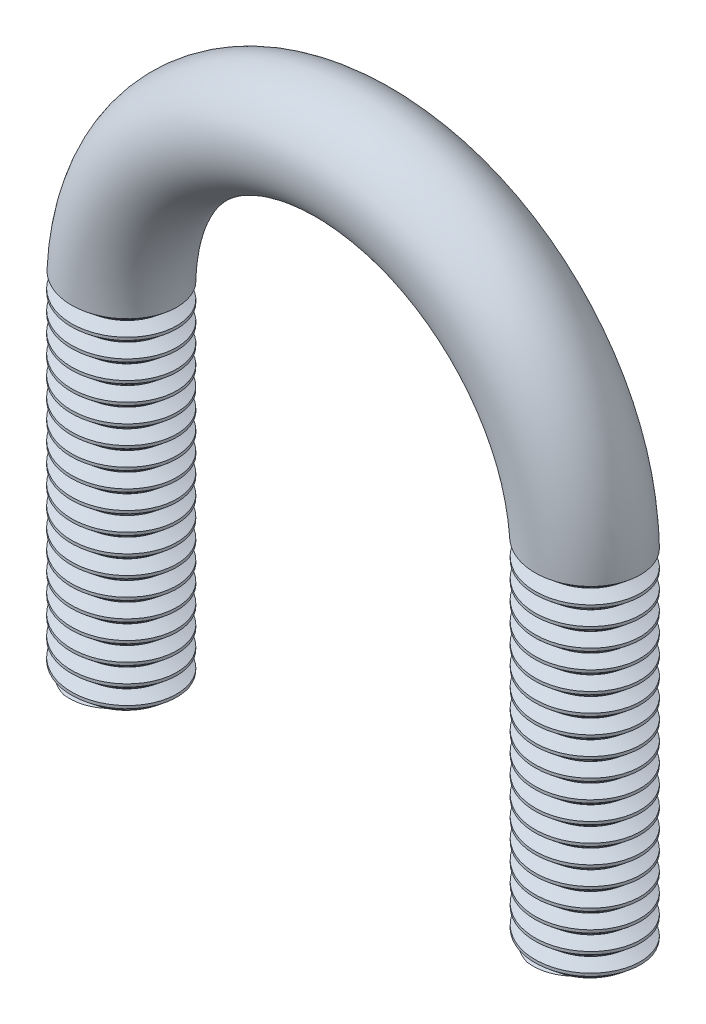
SolidWorks part; units mm, degrees
material "AISI 1020"
ref_plane "Front" through (0, 0, 0) normal (0, 0, 1) x (1, 0, 0)
ref_plane "Top" through (0, 0, 0) normal (0, 1, 0) x (1, 0, 0)
ref_plane "Right" through (0, 0, 0) normal (1, 0, 0) x (0, 0, -1)
sketch "Sketch1" plane through (0, 0, 0) normal (0, 0, 1) x (1, 0, 0)
  line L0 (17.4308, -8.251) -> (17.4308, 17.235)
  line L2 (-17.4308, -8.251) -> (-17.4308, 17.235)
  line L4 (0, -14.6685) -> (0, 64.7717) construction
  arc A0 (17.4308, 17.235) -> (-17.4308, 17.235) centre (0, 17.235) ccw
  dimension "0.61*TubeDia" = 17.4308
  dimension "0.28875*TubeDia" = 8.251
  dimension "0.8919*TubeDia" = 25.486
ref_plane "Plane1" through (0, -8.251, 0) normal (0, 1, 0) x (1, 0, 0)
sketch "Sketch2" plane through (0, -8.251, 0) normal (0, 1, 0) x (1, 0, 0)
  line L0 (-17.4308, 0) -> (17.4308, 0) construction
  circle A0 centre (-17.4308, 0) radius 3.9687
  dimension "D1" = 7.9375
sweep "Sweep1" add profiles "Sketch2" path "Sketch1"
chamfer "Chamfer1" distance 0.508 angle 45 2 edges at (17.4308, -8.251, 3.9687) (-17.4308, -8.251, 3.9687)
ref_plane "Plane2" through (0, -10.791, 0) normal (0, 1, 0) x (1, 0, 0)
sketch "Sketch3" plane through (0, -10.791, 0) normal (0, 1, 0) x (1, 0, 0)
  circle A0 centre (-17.4308, 0) radius 3.9688
  circle A1 centre (-17.4308, 0) radius 3.9687 construction
curve "Helix/Spiral1" pitch 1.4111 height 28.575 radius 3.9688 left hand yes centre (-17.4308, -10.791, 0) axis (0, 1, 0) start towards (0, 0, 1) parameters "0.5625*TubeDia"=28.575, "ThreadLead"=1.4111
sketch "Sketch4" plane through (0, 0, 0) normal (0, 0, 1) x (1, 0, 0)
  line L0 (-21.3995, 17.235) -> (-21.3995, -7.743) construction
  line L1 (-20.3967, 17.6207) -> (-21.7595, 18.734)
  line L2 (-21.7595, 18.734) -> (-22.0423, 16.9971)
  line L3 (-22.0423, 16.9971) -> (-20.3967, 17.6207)
  circle A0 centre (-21.3995, 17.784) radius 0.508 construction
  spline S0 degree 3 poles (-17.4308, -10.791) (-17.9469, -10.7618) (-18.9906, -10.7027) (-20.3097, -10.6147) (-21.193, -10.5264) (-21.5028, -10.4383) (-21.1929, -10.3501) (-20.3101, -10.2619) (-18.9891, -10.1737) (-17.4307, -10.0855) (-15.8724, -9.9973) (-14.5514, -9.9091) (-13.6686, -9.8209) (-13.3587, -9.7327) (-13.6686, -9.6445) (-14.5514, -9.5563) (-15.8724, -9.4681) (-17.4307, -9.3799) (-18.9891, -9.2917) (-20.3101, -9.2035) (-21.1929, -9.1153) (-21.5028, -9.0271) (-21.1929, -8.9389) (-20.3101, -8.8508) (-18.9891, -8.7626) (-17.4307, -8.6744) (-15.8724, -8.5862) (-14.5514, -8.498) (-13.6686, -8.4098) (-13.3587, -8.3216) (-13.6686, -8.2334) (-14.5514, -8.1452) (-15.8724, -8.057) (-17.4308, -7.9688) (-18.9891, -7.8806) (-20.3101, -7.7924) (-21.1929, -7.7042) (-21.5028, -7.616) (-21.1929, -7.5278) (-20.3101, -7.4396) (-18.9891, -7.3514) (-17.4307, -7.2633) (-15.8724, -7.1751) (-14.5514, -7.0869) (-13.6686, -6.9987) (-13.3587, -6.9105) (-13.6686, -6.8223) (-14.5514, -6.7341) (-15.8724, -6.6459) (-17.4308, -6.5577) (-18.9891, -6.4695) (-20.3101, -6.3813) (-21.1929, -6.2931) (-21.5028, -6.2049) (-21.1929, -6.1167) (-20.3101, -6.0285) (-18.9891, -5.9403) (-17.4307, -5.8521) (-15.8724, -5.7639) (-14.5514, -5.6758) (-13.6686, -5.5876) (-13.3587, -5.4994) (-13.6686, -5.4112) (-14.5514, -5.323) (-15.8724, -5.2348) (-17.4308, -5.1466) (-18.9891, -5.0584) (-20.3101, -4.9702) (-21.1929, -4.882) (-21.5028, -4.7938) (-21.1929, -4.7056) (-20.3101, -4.6174) (-18.9891, -4.5292) (-17.4307, -4.441) (-15.8724, -4.3528) (-14.5514, -4.2646) (-13.6686, -4.1764) (-13.3587, -4.0883) (-13.6686, -4.0001) (-14.5514, -3.9119) (-15.8724, -3.8237) (-17.4308, -3.7355) (-18.9891, -3.6473) (-20.3101, -3.5591) (-21.1929, -3.4709) (-21.5028, -3.3827) (-21.1929, -3.2945) (-20.3101, -3.2063) (-18.9891, -3.1181) (-17.4307, -3.0299) (-15.8724, -2.9417) (-14.5514, -2.8535) (-13.6686, -2.7653) (-13.3587, -2.6771) (-13.6686, -2.5889) (-14.5514, -2.5008) (-15.8724, -2.4126) (-17.4308, -2.3244) (-18.9891, -2.2362) (-20.3101, -2.148) (-21.1929, -2.0598) (-21.5028, -1.9716) (-21.1929, -1.8834) (-20.3101, -1.7952) (-18.9891, -1.707) (-17.4307, -1.6188) (-15.8724, -1.5306) (-14.5514, -1.4424) (-13.6686, -1.3542) (-13.3587, -1.266) (-13.6686, -1.1778) (-14.5514, -1.0896) (-15.8724, -1.0014) (-17.4308, -0.9133) (-18.9891, -0.8251) (-20.3101, -0.7369) (-21.1929, -0.6487) (-21.5028, -0.5605) (-21.1929, -0.4723) (-20.3101, -0.3841) (-18.9891, -0.2959) (-17.4307, -0.2077) (-15.8724, -0.1195) (-14.5514, -0.0313) (-13.6686, 0.0569) (-13.3587, 0.1451) (-13.6686, 0.2333) (-14.5514, 0.3215) (-15.8724, 0.4097) (-17.4308, 0.4979) (-18.9891, 0.5861) (-20.3101, 0.6742) (-21.1929, 0.7624) (-21.5028, 0.8506) (-21.1929, 0.9388) (-20.3101, 1.027) (-18.9891, 1.1152) (-17.4307, 1.2034) (-15.8724, 1.2916) (-14.5514, 1.3798) (-13.6686, 1.468) (-13.3587, 1.5562) (-13.6686, 1.6444) (-14.5514, 1.7326) (-15.8724, 1.8208) (-17.4308, 1.909) (-18.9891, 1.9972) (-20.3101, 2.0854) (-21.1929, 2.1736) (-21.5028, 2.2617) (-21.1929, 2.3499) (-20.3101, 2.4381) (-18.9891, 2.5263) (-17.4307, 2.6145) (-15.8724, 2.7027) (-14.5514, 2.7909) (-13.6686, 2.8791) (-13.3587, 2.9673) (-13.6686, 3.0555) (-14.5514, 3.1437) (-15.8724, 3.2319) (-17.4308, 3.3201) (-18.9891, 3.4083) (-20.3101, 3.4965) (-21.1929, 3.5847) (-21.5028, 3.6729) (-21.1929, 3.7611) (-20.3101, 3.8492) (-18.9891, 3.9374) (-17.4307, 4.0256) (-15.8724, 4.1138) (-14.5514, 4.202) (-13.6686, 4.2902) (-13.3587, 4.3784) (-13.6686, 4.4666) (-14.5514, 4.5548) (-15.8724, 4.643) (-17.4308, 4.7312) (-18.9891, 4.8194) (-20.3101, 4.9076) (-21.1929, 4.9958) (-21.5028, 5.084) (-21.1929, 5.1722) (-20.3101, 5.2604) (-18.9891, 5.3486) (-17.4307, 5.4367) (-15.8724, 5.5249) (-14.5514, 5.6131) (-13.6686, 5.7013) (-13.3587, 5.7895) (-13.6686, 5.8777) (-14.5514, 5.9659) (-15.8724, 6.0541) (-17.4308, 6.1423) (-18.9891, 6.2305) (-20.3101, 6.3187) (-21.1929, 6.4069) (-21.5028, 6.4951) (-21.1929, 6.5833) (-20.3101, 6.6715) (-18.9891, 6.7597) (-17.4307, 6.8479) (-15.8724, 6.9361) (-14.5514, 7.0242) (-13.6686, 7.1124) (-13.3587, 7.2006) (-13.6686, 7.2888) (-14.5514, 7.377) (-15.8724, 7.4652) (-17.4308, 7.5534) (-18.9891, 7.6416) (-20.3101, 7.7298) (-21.1929, 7.818) (-21.5028, 7.9062) (-21.1929, 7.9944) (-20.3101, 8.0826) (-18.9891, 8.1708) (-17.4307, 8.259) (-15.8724, 8.3472) (-14.5514, 8.4354) (-13.6686, 8.5236) (-13.3587, 8.6117) (-13.6686, 8.6999) (-14.5514, 8.7881) (-15.8724, 8.8763) (-17.4308, 8.9645) (-18.9891, 9.0527) (-20.3101, 9.1409) (-21.1929, 9.2291) (-21.5028, 9.3173) (-21.1929, 9.4055) (-20.3101, 9.4937) (-18.9891, 9.5819) (-17.4307, 9.6701) (-15.8724, 9.7583) (-14.5514, 9.8465) (-13.6686, 9.9347) (-13.3587, 10.0229) (-13.6686, 10.1111) (-14.5514, 10.1992) (-15.8724, 10.2874) (-17.4308, 10.3756) (-18.9891, 10.4638) (-20.3101, 10.552) (-21.1929, 10.6402) (-21.5028, 10.7284) (-21.1929, 10.8166) (-20.3101, 10.9048) (-18.9891, 10.993) (-17.4307, 11.0812) (-15.8724, 11.1694) (-14.5514, 11.2576) (-13.6686, 11.3458) (-13.3587, 11.434) (-13.6686, 11.5222) (-14.5514, 11.6104) (-15.8724, 11.6986) (-17.4308, 11.7867) (-18.9891, 11.8749) (-20.3101, 11.9631) (-21.1929, 12.0513) (-21.5028, 12.1395) (-21.1929, 12.2277) (-20.3101, 12.3159) (-18.9891, 12.4041) (-17.4307, 12.4923) (-15.8724, 12.5805) (-14.5514, 12.6687) (-13.6686, 12.7569) (-13.3587, 12.8451) (-13.6686, 12.9333) (-14.5514, 13.0215) (-15.8724, 13.1097) (-17.4308, 13.1979) (-18.9891, 13.2861) (-20.3101, 13.3742) (-21.1929, 13.4624) (-21.5028, 13.5506) (-21.1929, 13.6388) (-20.3101, 13.727) (-18.9891, 13.8152) (-17.4307, 13.9034) (-15.8724, 13.9916) (-14.5514, 14.0798) (-13.6686, 14.168) (-13.3587, 14.2562) (-13.6686, 14.3444) (-14.5514, 14.4326) (-15.8724, 14.5208) (-17.4308, 14.609) (-18.9891, 14.6972) (-20.3101, 14.7854) (-21.1929, 14.8736) (-21.5028, 14.9617) (-21.1929, 15.0499) (-20.3101, 15.1381) (-18.9891, 15.2263) (-17.4307, 15.3145) (-15.8724, 15.4027) (-14.5514, 15.4909) (-13.6686, 15.5791) (-13.3587, 15.6673) (-13.6686, 15.7555) (-14.5514, 15.8437) (-15.8724, 15.9319) (-17.4308, 16.0201) (-18.9891, 16.1083) (-20.3101, 16.1965) (-21.1929, 16.2847) (-21.5028, 16.3729) (-21.1929, 16.4611) (-20.3101, 16.5492) (-18.9891, 16.6374) (-17.4307, 16.7256) (-15.8724, 16.8138) (-14.5514, 16.902) (-13.6686, 16.9902) (-13.3587, 17.0784) (-13.6686, 17.1666) (-14.5514, 17.2548) (-15.8724, 17.343) (-17.4308, 17.4312) (-18.9891, 17.5194) (-20.3101, 17.6076) (-21.1929, 17.6957) (-21.3995, 17.7548) (-21.3995, 17.784) knots 0 0 0 0 0.003086 0.006173 0.009259 0.012346 0.015432 0.018519 0.021605 0.024691 0.027778 0.030864 0.033951 0.037037 0.040123 0.04321 0.046296 0.049383 0.052469 0.055556 0.058642 0.061728 0.064815 0.067901 0.070988 0.074074 0.07716 0.080247 0.083333 0.08642 0.089506 0.092593 0.095679 0.098765 0.101852 0.104938 0.108025 0.111111 0.114198 0.117284 0.12037 0.123457 0.126543 0.12963 0.132716 0.135802 0.138889 0.141975 0.145062 0.148148 0.151235 0.154321 0.157407 0.160494 0.16358 0.166667 0.169753 0.17284 0.175926 0.179012 0.182099 0.185185 0.188272 0.191358 0.194444 0.197531 0.200617 0.203704 0.20679 0.209877 0.212963 0.216049 0.219136 0.222222 0.225309 0.228395 0.231481 0.234568 0.237654 0.240741 0.243827 0.246914 0.25 0.253086 0.256173 0.259259 0.262346 0.265432 0.268519 0.271605 0.274691 0.277778 0.280864 0.283951 0.287037 0.290123 0.29321 0.296296 0.299383 0.302469 0.305556 0.308642 0.311728 0.314815 0.317901 0.320988 0.324074 0.32716 0.330247 0.333333 0.33642 0.339506 0.342593 0.345679 0.348765 0.351852 0.354938 0.358025 0.361111 0.364198 0.367284 0.37037 0.373457 0.376543 0.37963 0.382716 0.385802 0.388889 0.391975 0.395062 0.398148 0.401235 0.404321 0.407407 0.410494 0.41358 0.416667 0.419753 0.42284 0.425926 0.429012 0.432099 0.435185 0.438272 0.441358 0.444444 0.447531 0.450617 0.453704 0.45679 0.459877 0.462963 0.466049 0.469136 0.472222 0.475309 0.478395 0.481481 0.484568 0.487654 0.490741 0.493827 0.496914 0.5 0.503086 0.506173 0.509259 0.512346 0.515432 0.518519 0.521605 0.524691 0.527778 0.530864 0.533951 0.537037 0.540123 0.54321 0.546296 0.549383 0.552469 0.555556 0.558642 0.561728 0.564815 0.567901 0.570988 0.574074 0.57716 0.580247 0.583333 0.58642 0.589506 0.592593 0.595679 0.598765 0.601852 0.604938 0.608025 0.611111 0.614198 0.617284 0.62037 0.623457 0.626543 0.62963 0.632716 0.635802 0.638889 0.641975 0.645062 0.648148 0.651235 0.654321 0.657407 0.660494 0.66358 0.666667 0.669753 0.67284 0.675926 0.679012 0.682099 0.685185 0.688272 0.691358 0.694444 0.697531 0.700617 0.703704 0.70679 0.709877 0.712963 0.716049 0.719136 0.722222 0.725309 0.728395 0.731481 0.734568 0.737654 0.740741 0.743827 0.746914 0.75 0.753086 0.756173 0.759259 0.762346 0.765432 0.768519 0.771605 0.774691 0.777778 0.780864 0.783951 0.787037 0.790123 0.79321 0.796296 0.799383 0.802469 0.805556 0.808642 0.811728 0.814815 0.817901 0.820988 0.824074 0.82716 0.830247 0.833333 0.83642 0.839506 0.842593 0.845679 0.848765 0.851852 0.854938 0.858025 0.861111 0.864198 0.867284 0.87037 0.873457 0.876543 0.87963 0.882716 0.885802 0.888889 0.891975 0.895062 0.898148 0.901235 0.904321 0.907407 0.910494 0.91358 0.916667 0.919753 0.92284 0.925926 0.929012 0.932099 0.935185 0.938272 0.941358 0.944444 0.947531 0.950617 0.953704 0.95679 0.959877 0.962963 0.966049 0.969136 0.972222 0.975309 0.978395 0.981481 0.984568 0.987654 0.990741 0.993827 0.996914 1 1 1 1 construction
  dimension "ThdDepth" = 1.016
sweep "Cut-Sweep1" cut profiles "Sketch4" path "Helix/Spiral1"
sketch "Sketch5" plane through (0, -10.791, 0) normal (0, 1, 0) x (1, 0, 0)
  circle A0 centre (17.4308, 0) radius 3.9687
  circle A1 centre (17.4308, 0) radius 3.9687 construction
curve "Helix/Spiral2" pitch 1.4111 height 28.575 radius 3.9687 left hand yes centre (17.4308, -10.791, 0) axis (0, 1, 0) start towards (0, 0, 1) parameters "ThdLength"=28.575
sketch "Sketch6" plane through (0, 0, 0) normal (0, 0, 1) x (1, 0, 0)
  line L0 (13.462, 17.235) -> (13.462, -7.743) construction
  line L1 (14.4648, 17.6207) -> (13.102, 18.734)
  line L2 (13.102, 18.734) -> (12.8192, 16.9971)
  line L3 (12.8192, 16.9971) -> (14.4648, 17.6207)
  circle A0 centre (13.462, 17.784) radius 0.508 construction
  spline S0 degree 3 poles (17.4308, -10.791) (16.9146, -10.7618) (15.8709, -10.7027) (14.5518, -10.6147) (13.6685, -10.5264) (13.3587, -10.4383) (13.6686, -10.3501) (14.5514, -10.2619) (15.8724, -10.1737) (17.4308, -10.0855) (18.9891, -9.9973) (20.3101, -9.9091) (21.1929, -9.8209) (21.5028, -9.7327) (21.1929, -9.6445) (20.3101, -9.5563) (18.9891, -9.4681) (17.4308, -9.3799) (15.8724, -9.2917) (14.5514, -9.2035) (13.6686, -9.1153) (13.3587, -9.0271) (13.6686, -8.9389) (14.5514, -8.8508) (15.8724, -8.7626) (17.4308, -8.6744) (18.9891, -8.5862) (20.3101, -8.498) (21.1929, -8.4098) (21.5028, -8.3216) (21.1929, -8.2334) (20.3101, -8.1452) (18.9891, -8.057) (17.4307, -7.9688) (15.8724, -7.8806) (14.5514, -7.7924) (13.6686, -7.7042) (13.3587, -7.616) (13.6686, -7.5278) (14.5514, -7.4396) (15.8724, -7.3514) (17.4308, -7.2633) (18.9891, -7.1751) (20.3101, -7.0869) (21.1929, -6.9987) (21.5028, -6.9105) (21.1929, -6.8223) (20.3101, -6.7341) (18.9891, -6.6459) (17.4307, -6.5577) (15.8724, -6.4695) (14.5514, -6.3813) (13.6686, -6.2931) (13.3587, -6.2049) (13.6686, -6.1167) (14.5514, -6.0285) (15.8724, -5.9403) (17.4308, -5.8521) (18.9891, -5.7639) (20.3101, -5.6758) (21.1929, -5.5876) (21.5028, -5.4994) (21.1929, -5.4112) (20.3101, -5.323) (18.9891, -5.2348) (17.4307, -5.1466) (15.8724, -5.0584) (14.5514, -4.9702) (13.6686, -4.882) (13.3587, -4.7938) (13.6686, -4.7056) (14.5514, -4.6174) (15.8724, -4.5292) (17.4308, -4.441) (18.9891, -4.3528) (20.3101, -4.2646) (21.1929, -4.1764) (21.5028, -4.0883) (21.1929, -4.0001) (20.3101, -3.9119) (18.9891, -3.8237) (17.4307, -3.7355) (15.8724, -3.6473) (14.5514, -3.5591) (13.6686, -3.4709) (13.3587, -3.3827) (13.6686, -3.2945) (14.5514, -3.2063) (15.8724, -3.1181) (17.4308, -3.0299) (18.9891, -2.9417) (20.3101, -2.8535) (21.1929, -2.7653) (21.5028, -2.6771) (21.1929, -2.5889) (20.3101, -2.5008) (18.9891, -2.4126) (17.4307, -2.3244) (15.8724, -2.2362) (14.5514, -2.148) (13.6686, -2.0598) (13.3587, -1.9716) (13.6686, -1.8834) (14.5514, -1.7952) (15.8724, -1.707) (17.4308, -1.6188) (18.9891, -1.5306) (20.3101, -1.4424) (21.1929, -1.3542) (21.5028, -1.266) (21.1929, -1.1778) (20.3101, -1.0896) (18.9891, -1.0014) (17.4307, -0.9133) (15.8724, -0.8251) (14.5514, -0.7369) (13.6686, -0.6487) (13.3587, -0.5605) (13.6686, -0.4723) (14.5514, -0.3841) (15.8724, -0.2959) (17.4308, -0.2077) (18.9891, -0.1195) (20.3101, -0.0313) (21.1929, 0.0569) (21.5028, 0.1451) (21.1929, 0.2333) (20.3101, 0.3215) (18.9891, 0.4097) (17.4307, 0.4979) (15.8724, 0.5861) (14.5514, 0.6742) (13.6686, 0.7624) (13.3587, 0.8506) (13.6686, 0.9388) (14.5514, 1.027) (15.8724, 1.1152) (17.4308, 1.2034) (18.9891, 1.2916) (20.3101, 1.3798) (21.1929, 1.468) (21.5028, 1.5562) (21.1929, 1.6444) (20.3101, 1.7326) (18.9891, 1.8208) (17.4307, 1.909) (15.8724, 1.9972) (14.5514, 2.0854) (13.6686, 2.1736) (13.3587, 2.2617) (13.6686, 2.3499) (14.5514, 2.4381) (15.8724, 2.5263) (17.4308, 2.6145) (18.9891, 2.7027) (20.3101, 2.7909) (21.1929, 2.8791) (21.5028, 2.9673) (21.1929, 3.0555) (20.3101, 3.1437) (18.9891, 3.2319) (17.4307, 3.3201) (15.8724, 3.4083) (14.5514, 3.4965) (13.6686, 3.5847) (13.3587, 3.6729) (13.6686, 3.7611) (14.5514, 3.8492) (15.8724, 3.9374) (17.4308, 4.0256) (18.9891, 4.1138) (20.3101, 4.202) (21.1929, 4.2902) (21.5028, 4.3784) (21.1929, 4.4666) (20.3101, 4.5548) (18.9891, 4.643) (17.4307, 4.7312) (15.8724, 4.8194) (14.5514, 4.9076) (13.6686, 4.9958) (13.3587, 5.084) (13.6686, 5.1722) (14.5514, 5.2604) (15.8724, 5.3486) (17.4308, 5.4367) (18.9891, 5.5249) (20.3101, 5.6131) (21.1929, 5.7013) (21.5028, 5.7895) (21.1929, 5.8777) (20.3101, 5.9659) (18.9891, 6.0541) (17.4307, 6.1423) (15.8724, 6.2305) (14.5514, 6.3187) (13.6686, 6.4069) (13.3587, 6.4951) (13.6686, 6.5833) (14.5514, 6.6715) (15.8724, 6.7597) (17.4308, 6.8479) (18.9891, 6.9361) (20.3101, 7.0242) (21.1929, 7.1124) (21.5028, 7.2006) (21.1929, 7.2888) (20.3101, 7.377) (18.9891, 7.4652) (17.4307, 7.5534) (15.8724, 7.6416) (14.5514, 7.7298) (13.6686, 7.818) (13.3587, 7.9062) (13.6686, 7.9944) (14.5514, 8.0826) (15.8724, 8.1708) (17.4308, 8.259) (18.9891, 8.3472) (20.3101, 8.4354) (21.1929, 8.5236) (21.5028, 8.6117) (21.1929, 8.6999) (20.3101, 8.7881) (18.9891, 8.8763) (17.4307, 8.9645) (15.8724, 9.0527) (14.5514, 9.1409) (13.6686, 9.2291) (13.3587, 9.3173) (13.6686, 9.4055) (14.5514, 9.4937) (15.8724, 9.5819) (17.4308, 9.6701) (18.9891, 9.7583) (20.3101, 9.8465) (21.1929, 9.9347) (21.5028, 10.0229) (21.1929, 10.1111) (20.3101, 10.1992) (18.9891, 10.2874) (17.4307, 10.3756) (15.8724, 10.4638) (14.5514, 10.552) (13.6686, 10.6402) (13.3587, 10.7284) (13.6686, 10.8166) (14.5514, 10.9048) (15.8724, 10.993) (17.4308, 11.0812) (18.9891, 11.1694) (20.3101, 11.2576) (21.1929, 11.3458) (21.5028, 11.434) (21.1929, 11.5222) (20.3101, 11.6104) (18.9891, 11.6986) (17.4307, 11.7867) (15.8724, 11.8749) (14.5514, 11.9631) (13.6686, 12.0513) (13.3587, 12.1395) (13.6686, 12.2277) (14.5514, 12.3159) (15.8724, 12.4041) (17.4308, 12.4923) (18.9891, 12.5805) (20.3101, 12.6687) (21.1929, 12.7569) (21.5028, 12.8451) (21.1929, 12.9333) (20.3101, 13.0215) (18.9891, 13.1097) (17.4307, 13.1979) (15.8724, 13.2861) (14.5514, 13.3742) (13.6686, 13.4624) (13.3587, 13.5506) (13.6686, 13.6388) (14.5514, 13.727) (15.8724, 13.8152) (17.4308, 13.9034) (18.9891, 13.9916) (20.3101, 14.0798) (21.1929, 14.168) (21.5028, 14.2562) (21.1929, 14.3444) (20.3101, 14.4326) (18.9891, 14.5208) (17.4307, 14.609) (15.8724, 14.6972) (14.5514, 14.7854) (13.6686, 14.8736) (13.3587, 14.9617) (13.6686, 15.0499) (14.5514, 15.1381) (15.8724, 15.2263) (17.4308, 15.3145) (18.9891, 15.4027) (20.3101, 15.4909) (21.1929, 15.5791) (21.5028, 15.6673) (21.1929, 15.7555) (20.3101, 15.8437) (18.9891, 15.9319) (17.4307, 16.0201) (15.8724, 16.1083) (14.5514, 16.1965) (13.6686, 16.2847) (13.3587, 16.3729) (13.6686, 16.4611) (14.5514, 16.5492) (15.8724, 16.6374) (17.4308, 16.7256) (18.9891, 16.8138) (20.3101, 16.902) (21.1929, 16.9902) (21.5028, 17.0784) (21.1929, 17.1666) (20.3101, 17.2548) (18.9891, 17.343) (17.4307, 17.4312) (15.8724, 17.5194) (14.5514, 17.6076) (13.6686, 17.6957) (13.462, 17.7548) (13.462, 17.784) knots 0 0 0 0 0.003086 0.006173 0.009259 0.012346 0.015432 0.018519 0.021605 0.024691 0.027778 0.030864 0.033951 0.037037 0.040123 0.04321 0.046296 0.049383 0.052469 0.055556 0.058642 0.061728 0.064815 0.067901 0.070988 0.074074 0.07716 0.080247 0.083333 0.08642 0.089506 0.092593 0.095679 0.098765 0.101852 0.104938 0.108025 0.111111 0.114198 0.117284 0.12037 0.123457 0.126543 0.12963 0.132716 0.135802 0.138889 0.141975 0.145062 0.148148 0.151235 0.154321 0.157407 0.160494 0.16358 0.166667 0.169753 0.17284 0.175926 0.179012 0.182099 0.185185 0.188272 0.191358 0.194444 0.197531 0.200617 0.203704 0.20679 0.209877 0.212963 0.216049 0.219136 0.222222 0.225309 0.228395 0.231481 0.234568 0.237654 0.240741 0.243827 0.246914 0.25 0.253086 0.256173 0.259259 0.262346 0.265432 0.268519 0.271605 0.274691 0.277778 0.280864 0.283951 0.287037 0.290123 0.29321 0.296296 0.299383 0.302469 0.305556 0.308642 0.311728 0.314815 0.317901 0.320988 0.324074 0.32716 0.330247 0.333333 0.33642 0.339506 0.342593 0.345679 0.348765 0.351852 0.354938 0.358025 0.361111 0.364198 0.367284 0.37037 0.373457 0.376543 0.37963 0.382716 0.385802 0.388889 0.391975 0.395062 0.398148 0.401235 0.404321 0.407407 0.410494 0.41358 0.416667 0.419753 0.42284 0.425926 0.429012 0.432099 0.435185 0.438272 0.441358 0.444444 0.447531 0.450617 0.453704 0.45679 0.459877 0.462963 0.466049 0.469136 0.472222 0.475309 0.478395 0.481481 0.484568 0.487654 0.490741 0.493827 0.496914 0.5 0.503086 0.506173 0.509259 0.512346 0.515432 0.518519 0.521605 0.524691 0.527778 0.530864 0.533951 0.537037 0.540123 0.54321 0.546296 0.549383 0.552469 0.555556 0.558642 0.561728 0.564815 0.567901 0.570988 0.574074 0.57716 0.580247 0.583333 0.58642 0.589506 0.592593 0.595679 0.598765 0.601852 0.604938 0.608025 0.611111 0.614198 0.617284 0.62037 0.623457 0.626543 0.62963 0.632716 0.635802 0.638889 0.641975 0.645062 0.648148 0.651235 0.654321 0.657407 0.660494 0.66358 0.666667 0.669753 0.67284 0.675926 0.679012 0.682099 0.685185 0.688272 0.691358 0.694444 0.697531 0.700617 0.703704 0.70679 0.709877 0.712963 0.716049 0.719136 0.722222 0.725309 0.728395 0.731481 0.734568 0.737654 0.740741 0.743827 0.746914 0.75 0.753086 0.756173 0.759259 0.762346 0.765432 0.768519 0.771605 0.774691 0.777778 0.780864 0.783951 0.787037 0.790123 0.79321 0.796296 0.799383 0.802469 0.805556 0.808642 0.811728 0.814815 0.817901 0.820988 0.824074 0.82716 0.830247 0.833333 0.83642 0.839506 0.842593 0.845679 0.848765 0.851852 0.854938 0.858025 0.861111 0.864198 0.867284 0.87037 0.873457 0.876543 0.87963 0.882716 0.885802 0.888889 0.891975 0.895062 0.898148 0.901235 0.904321 0.907407 0.910494 0.91358 0.916667 0.919753 0.92284 0.925926 0.929012 0.932099 0.935185 0.938272 0.941358 0.944444 0.947531 0.950617 0.953704 0.95679 0.959877 0.962963 0.966049 0.969136 0.972222 0.975309 0.978395 0.981481 0.984568 0.987654 0.990741 0.993827 0.996914 1 1 1 1 construction
  dimension "ThdDepth" = 1.016
sweep "Cut-Sweep2" cut profiles "Sketch6" path "Helix/Spiral2"
equation "\"ThdLength@Helix/Spiral2\"=\"0.5625*TubeDia@Helix/Spiral1\""
